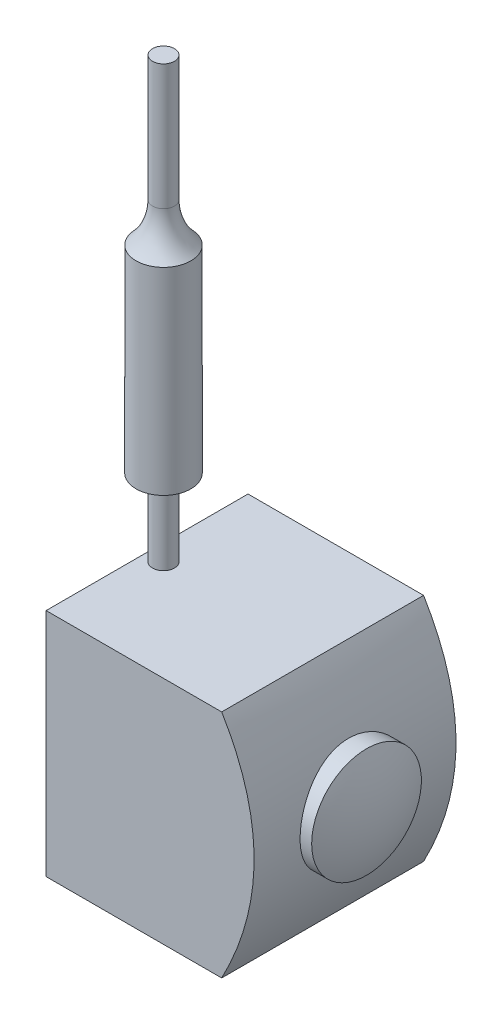
SolidWorks part; units mm, degrees
ref_plane "Front Plane" through (0, 0, 0) normal (0, 0, 1) x (1, 0, 0)
ref_plane "Top Plane" through (0, 0, 0) normal (0, 1, 0) x (1, 0, 0)
ref_plane "Right Plane" through (0, 0, 0) normal (1, 0, 0) x (0, 0, -1)
sketch "Sketch1" plane through (0, 0, 0) normal (0, 0, 1) x (1, 0, 0)
  line L1 (-17.5639, 9.9117) -> (-1.5639, 9.9117)
  line L2 (-17.5639, 9.9117) -> (-17.5639, -11.0883)
  line L3 (-17.5639, -11.0883) -> (-1.5639, -11.0883)
  spline S0 degree 2 poles (-1.5639, 9.9117) (4.3404, 0.1195) (-1.5639, -11.0883) knots 0 0 0 1 1 1
  dimension "D1" = 21
extrude "Boss-Extrude1" add sketch "Sketch1" along normal blind 18.4
sketch "Sketch2" plane through (-17.5639, 0, 0) normal (-1, 0, 0) x (0, 0, 1)
  line L0 (9.2, 9.9117) -> (9.2, -11.0883) construction
  line L1 (18.4, 9.9117) -> (0, 9.9117) construction
  line L2 (18.4, -11.0883) -> (0, -11.0883) construction
  circle A0 centre (9.2, -0.5883) radius 5
  dimension "D1" = 10
extrude "Boss-Extrude2" add sketch "Sketch2" against normal blind 20
dome "Dome1" faces to dome 1 distance 1 reverse direction no elliptical dome no face at (2.4361, -0.5883, 14.2) parameters "D1"=1
sketch "Sketch3" plane through (0, 9.9117, 0) normal (0, 1, 0) x (1, 0, 0)
  line L0 (-17.5639, -9.2) -> (-1.5639, -9.2) construction
  line L1 (-17.5639, -18.4) -> (-17.5639, 0) construction
  line L2 (-1.5639, -18.4) -> (-1.5639, 0) construction
  circle A0 centre (-16.0675, -9.2) radius 1
  dimension "D1" = 2
extrude "Boss-Extrude3" add sketch "Sketch3" along normal blind 40
sketch "Sketch4" plane through (0, 49.9117, 0) normal (0, 1, 0) x (1, 0, 0)
  circle A0 centre (-16.0675, -9.2) radius 2.5
  dimension "D1" = 5
extrude "Boss-Extrude4" add sketch "Sketch4" against normal blind 18 from offset 15 offset against normal yes
fillet "Fillet1" radius 5 1 edges at (-16.0675, 34.9117, 10.2)
